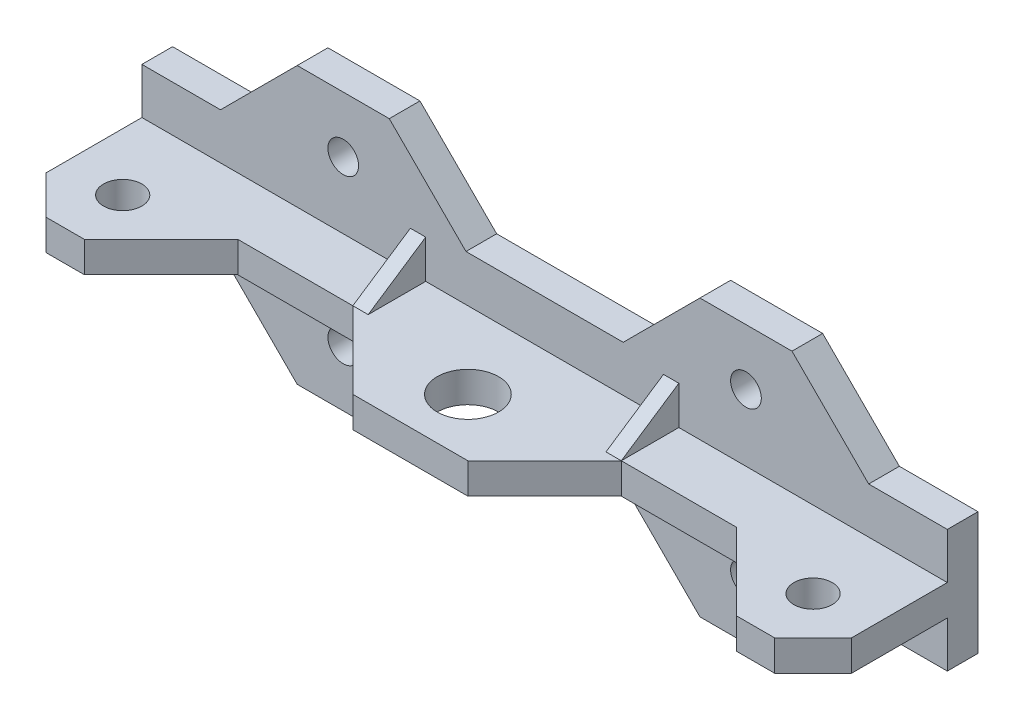
SolidWorks part; units mm, degrees
material "ABS"
ref_plane "Front Plane" through (0, 0, 0) normal (0, 0, 1) x (1, 0, 0)
ref_plane "Top Plane" through (0, 0, 0) normal (0, 1, 0) x (1, 0, 0)
ref_plane "Right Plane" through (0, 0, 0) normal (1, 0, 0) x (0, 0, -1)
sketch "Sketch2" plane through (0, 0, 0) normal (0, 1, 0) x (1, 0, 0)
  line L2 (-52.5, 10) -> (52.5, 10)
  line L27 (-45, 0) -> (45, 0) construction
  line L34 (-50.1202, 2.5) -> (-6.1027, 2.5) construction
  line L36 (0, 10) -> (0, -7.5) construction
  line L37 (7.5, -7.5) -> (-7.5, -7.5)
  line L40 (-32.5, 2.5) -> (-17.5, 2.5)
  line L41 (-17.5, 2.5) -> (-7.5, -7.5)
  line L42 (50.1202, 2.5) -> (6.1027, 2.5) construction
  line L48 (-52.5, 10) -> (-52.5, 0)
  line L50 (-52.5, -2.5) -> (-47.5, -7.5)
  line L52 (-52.5, 0) -> (-52.5, -2.5)
  line L53 (-47.5, -7.5) -> (-42.5, -7.5)
  line L55 (-42.5, -7.5) -> (-32.5, 2.5)
  line L56 (42.5, -7.5) -> (32.5, 2.5)
  line L57 (47.5, -7.5) -> (42.5, -7.5)
  line L58 (52.5, 0) -> (52.5, -2.5)
  line L59 (52.5, -2.5) -> (47.5, -7.5)
  line L60 (52.5, 10) -> (52.5, 0)
  line L61 (17.5, 2.5) -> (7.5, -7.5)
  line L62 (32.5, 2.5) -> (17.5, 2.5)
  circle A0 centre (0, 0) radius 4
  circle A1 centre (-45, 0) radius 2.5
  circle A3 centre (45, 0) radius 2.5
  point P8 (-52.5, -7.5)
  point P9 (-52.5, -7.5)
  point P23 (0, -10)
  point P34 (52.5, -7.5)
  dimension "D1" = 8
  dimension "D2" = 5
  dimension "D3" = 10
  dimension "D4" = 45
  dimension "D5" = 5
  dimension "D6" = 7.5
  dimension "D7" = 45
  dimension "D8" = 7.5
  dimension "D9" = 45
  dimension "D10" = 17.5
  dimension "D11" = 7.5
  dimension "D12" = 0
  dimension "D14" = 7.5
extrude "Boss-Extrude1" add sketch "Sketch2" along normal blind 2 and the other way blind 2
sketch "Sketch4" plane through (0, 0, -10) normal (0, 0, -1) x (-1, 0, 0)
  line L1 (52.5, -18) -> (-52.5, -18) construction
  line L3 (52.5, 18) -> (-52.5, 18) construction
  line L6 (52.5, -8) -> (42.25, -8)
  line L7 (42.25, -8) -> (32.25, -18)
  line L8 (20.25, -18) -> (10.25, -8)
  line L9 (10.25, -8) -> (-10.25, -8)
  line L10 (52.5, 0) -> (-52.5, 0) construction
  line L11 (0, -18) -> (0, 0) construction
  line L12 (32.25, -18) -> (20.25, -18)
  line L13 (0, -3.3494) -> (52.5, -3.3494) construction
  line L14 (26.25, -3.3494) -> (26.25, -18) construction
  line L15 (52.5, -8) -> (52.5, 8)
  line L16 (-20.25, -18) -> (-10.25, -8)
  line L17 (-32.25, -18) -> (-20.25, -18)
  line L18 (-42.25, -8) -> (-32.25, -18)
  line L19 (-52.5, -8) -> (-42.25, -8)
  line L20 (-52.5, -8) -> (-52.5, 8)
  line L21 (-52.5, 8) -> (-42.25, 8)
  line L22 (-42.25, 8) -> (-32.25, 18)
  line L23 (-32.25, 18) -> (-20.25, 18)
  line L24 (-20.25, 18) -> (-10.25, 8)
  line L25 (10.25, 8) -> (-10.25, 8)
  line L26 (20.25, 18) -> (10.25, 8)
  line L27 (32.25, 18) -> (20.25, 18)
  line L28 (42.25, 8) -> (32.25, 18)
  line L29 (52.5, 8) -> (42.25, 8)
  circle A0 centre (26.25, -10.6747) radius 2
  circle A1 centre (-26.25, -10.6747) radius 2
  circle A2 centre (-26.25, 10.6747) radius 2
  circle A3 centre (26.25, 10.6747) radius 2
  point P26 (0, -8)
  point P30 (-26.25, -18)
  dimension "D5" = 4
  dimension "D1" = 8
  dimension "D2" = 18
  dimension "D3" = 12
  dimension "D4" = 135
extrude "Boss-Extrude2" add sketch "Sketch4" along normal blind 4
ref_plane "Plane1" through (-17.5, 0, 0) normal (-1, 0, 0) x (0, 0, 1)
sketch "Sketch5" plane through (-17.5, 0, 0) normal (-1, 0, 0) x (0, 0, 1)
  line L3 (0, 0) -> (-3.5975, 0) construction
  line L4 (-10, 7) -> (-10, 2)
  line L5 (-2.5, 2) -> (-10, 7)
  line L7 (-10, 8) -> (-10, 2) construction
  line L8 (-2.5, 2) -> (-10, 2)
  line L9 (-2.5, -2) -> (-10, -7)
  line L10 (-10, -7) -> (-10, -2)
  line L11 (-2.5, -2) -> (-10, -2)
  dimension "D1" = 5
extrude "Boss-Extrude3" add sketch "Sketch5" against normal blind 2
mirror "Mirror1" about plane through (0, 0, 0) normal (1, 0, 0) of "Boss-Extrude3"
